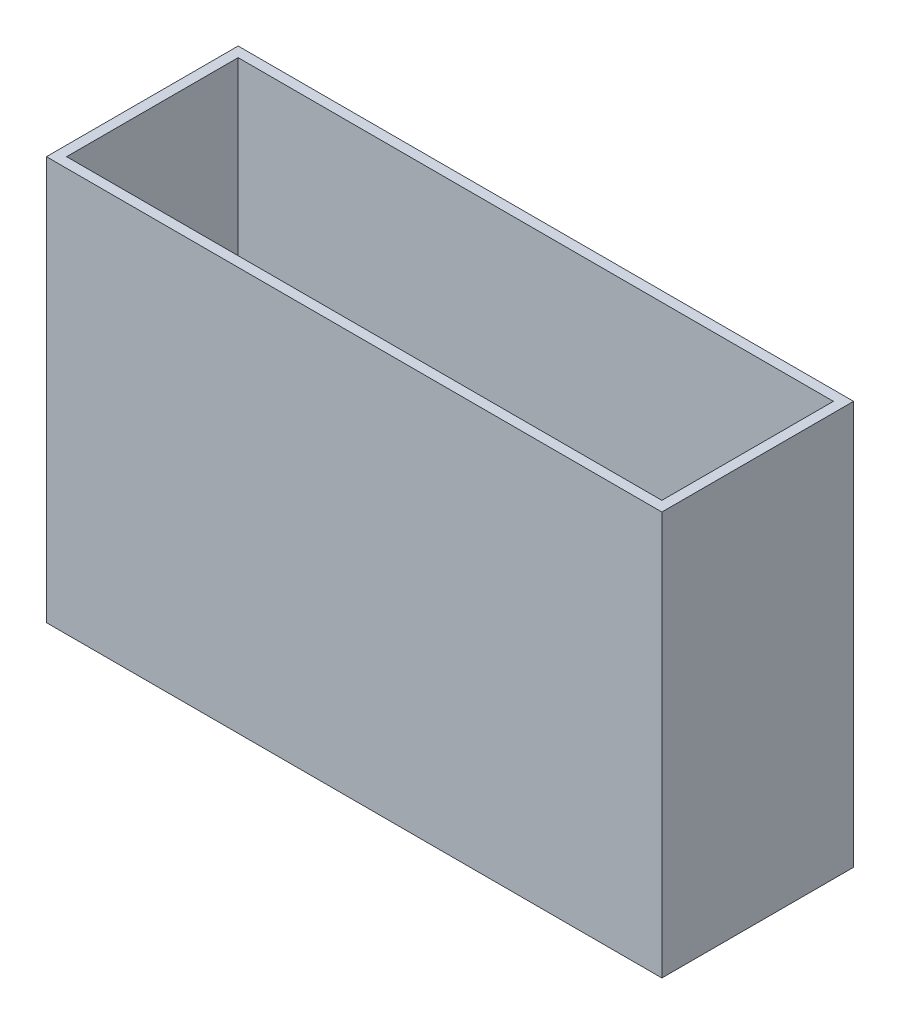
SolidWorks part; units mm, degrees
ref_plane "Front Plane" through (0, 0, 0) normal (0, 0, 1) x (1, 0, 0)
ref_plane "Top Plane" through (0, 0, 0) normal (0, 1, 0) x (1, 0, 0)
ref_plane "Right Plane" through (0, 0, 0) normal (1, 0, 0) x (0, 0, -1)
sketch "Sketch1" plane through (0, 0, 0) normal (0, 1, 0) x (1, 0, 0)
  line L0 (-14.75, 4.25) -> (-15.25, 4.25) construction
  line L1 (-14.75, 4.25) -> (14.75, 4.25)
  line L2 (-14.75, 4.25) -> (-14.75, -4.25)
  line L3 (-14.75, -4.25) -> (14.75, -4.25)
  line L4 (14.75, 4.25) -> (14.75, -4.25)
  line L5 (-14.75, 4.25) -> (14.75, -4.25) construction
  line L6 (-14.75, -4.25) -> (14.75, 4.25) construction
  line L7 (15.25, 4.75) -> (-15.25, 4.75)
  line L8 (15.25, 4.75) -> (15.25, -4.75)
  line L9 (15.25, -4.75) -> (-15.25, -4.75)
  line L10 (-15.25, 4.75) -> (-15.25, -4.75)
  line L11 (15.25, 4.75) -> (-15.25, -4.75) construction
  line L12 (15.25, -4.75) -> (-15.25, 4.75) construction
  line L13 (-14.75, 4.25) -> (-14.75, 4.75) construction
  point P0 (0, 0)
  point P6 (0, 0)
  dimension "D1" = 29.5
  dimension "D2" = 8.5
  dimension "D3" = 0.5
extrude "Boss-Extrude1" add sketch "Sketch1" along normal blind 20
